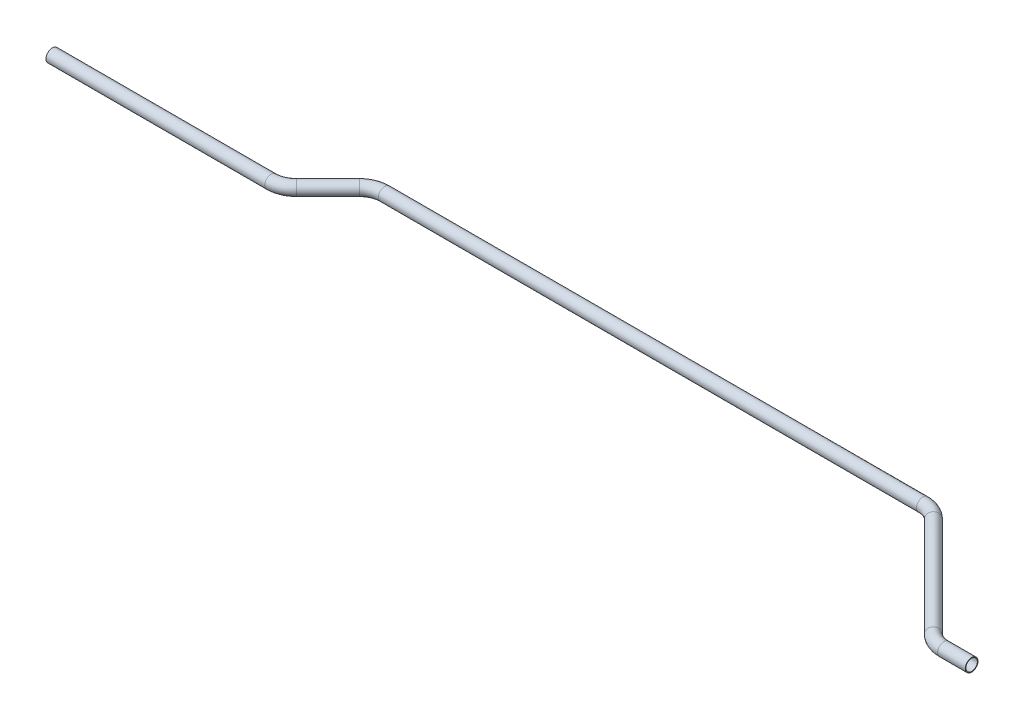
SolidWorks part; units mm, degrees
ref_plane "Front Plane" through (0, 0, 0) normal (0, 0, 1) x (1, 0, 0)
ref_plane "Top Plane" through (0, 0, 0) normal (0, 1, 0) x (1, 0, 0)
ref_plane "Right Plane" through (0, 0, 0) normal (1, 0, 0) x (0, 0, -1)
sketch "Sketch1" plane through (0, 0, 0) normal (0, 1, 0) x (1, 0, 0)
  line L0 (0, 0) -> (218.079, 0)
  line L1 (236.0395, 7.4395) -> (267.3044, 38.7044)
  line L2 (285.2649, 46.1439) -> (821.7554, 46.1439)
  line L3 (839.7159, 38.7044) -> (939.1369, -60.7167)
  line L4 (957.0974, -68.1561) -> (984.6764, -68.1561)
  arc A0 (939.1369, -60.7167) -> (957.0974, -68.1561) centre (957.0974, -42.7561) ccw
  arc A1 (821.7554, 46.1439) -> (839.7159, 38.7044) centre (821.7554, 20.7439) cw
  arc A2 (267.3044, 38.7044) -> (285.2649, 46.1439) centre (285.2649, 20.7439) cw
  arc A3 (218.079, 0) -> (236.0395, 7.4395) centre (218.079, 25.4) ccw
  point P9 (946.5764, -68.1561)
  point P12 (832.2764, 46.1439)
  point P15 (274.7439, 46.1439)
  point P18 (228.6, 0)
  dimension "D8" = 25.4
  dimension "D1" = 228.6
  dimension "D2" = 135
  dimension "D3" = 38.1
  dimension "D4" = 557.5325
  dimension "D5" = 114.3
  dimension "D6" = 45
  dimension "D7" = 46.1439
ref_plane "Plane1" through (0, 0, 0) normal (1, 0, 0) x (0, 0, -1)
sketch "Sketch2" plane through (0, 0, 0) normal (1, 0, 0) x (0, 0, -1)
  circle A0 centre (0, 0) radius 6.35
  circle A1 centre (0, 0) radius 5.715
  dimension "D1" = 12.7
  dimension "D2" = 0.635
sweep "Sweep1" add profiles "Sketch2" path "Sketch1"
